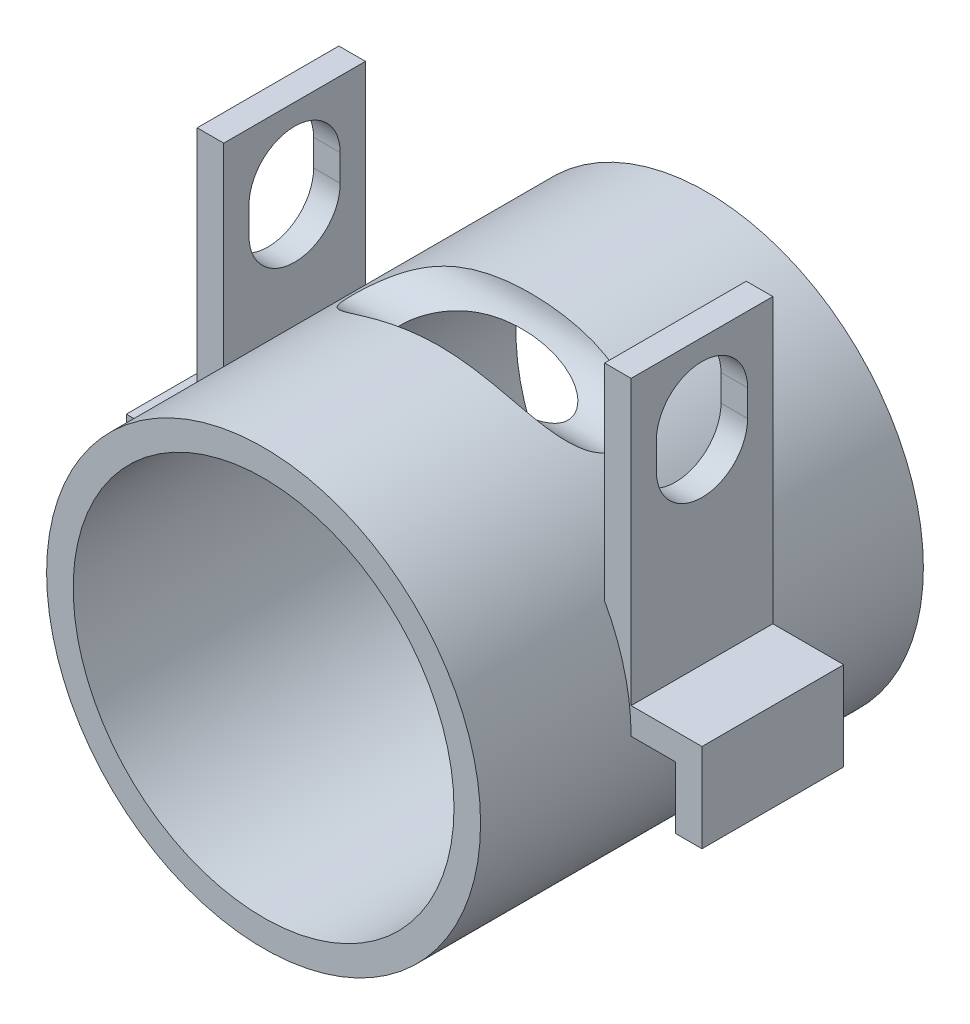
SolidWorks part; units mm, degrees
ref_plane "Front Plane" through (0, 0, 0) normal (0, 0, 1) x (1, 0, 0)
ref_plane "Top Plane" through (0, 0, 0) normal (0, 1, 0) x (1, 0, 0)
ref_plane "Right Plane" through (0, 0, 0) normal (1, 0, 0) x (0, 0, -1)
sketch "Sketch1" plane through (0, 0, 0) normal (0, 0, 1) x (1, 0, 0)
  circle A0 centre (0, 0) radius 21.5
  circle A1 centre (0, 0) radius 24.5
  dimension "D1" = 43
  dimension "D2" = 3
extrude "Boss-Extrude1" add sketch "Sketch1" along normal blind 50
ref_plane "Plane1" through (0, 0, 25) normal (0, 0, 1) x (1, 0, 0)
sketch "Sketch3" plane through (0, 0, 0) normal (1, 0, 0) x (0, 0, -1)
  line L0 (0, 24.5) -> (-50, 24.5) construction
  circle A0 centre (-25, 24.5) radius 5.15
  dimension "D1" = 10.3
extrude "Cut-Extrude1" cut sketch "Sketch3" against normal mid plane 50
sketch "Sketch4" plane through (0, 0, 25) normal (0, 0, 1) x (1, 0, 0)
  line L3 (0, 0) -> (50000, 0) construction
  line L4 (-19.776, 24.5) -> (49980.224, 24.5) construction
  line L5 (-21.5, 11.7473) -> (-21.5, 35)
  line L6 (-24.5, 0) -> (-24.5, 35)
  line L7 (-24.5, 35) -> (-21.5, 35)
  line L8 (0, 0) -> (0, 11.0861) construction
  circle A3 centre (0, 0) radius 24.5 construction
  arc A4 (-21.5, 11.7473) -> (-24.5, 0) centre (0, 0) ccw
  dimension "D1" = 3
  dimension "D2" = 35
extrude "Boss-Extrude2" add sketch "Sketch4" along normal mid plane 16
sketch "Sketch6" plane through (0, 0, 25) normal (0, 0, 1) x (1, 0, 0)
  line L0 (-24.5, 35) -> (-24.5, 0) construction
  line L1 (-24.5, 0) -> (-32.5, 0)
  line L2 (-24.5, 0) -> (-24.5, 3)
  line L3 (-24.5, 3) -> (-32.5, 3)
  line L4 (-32.5, 0) -> (-32.5, 3)
  line L5 (-24.5, 0) -> (-32.5, 3) construction
  line L6 (-24.5, 3) -> (-32.5, 0) construction
  line L7 (-32.5, 0) -> (-29.5, 0)
  line L8 (-32.5, 0) -> (-32.5, -7)
  line L9 (-32.5, -7) -> (-29.5, -7)
  line L10 (-29.5, 0) -> (-29.5, -7)
  line L11 (-32.5, 0) -> (-29.5, -7) construction
  line L12 (-32.5, -7) -> (-29.5, 0) construction
  circle A0 centre (0, 0) radius 24.5 construction
  arc A1 (-21.5, 11.7473) -> (-24.5, 0) centre (0, 0) ccw construction
  point P4 (-28.5, 1.5)
  point P13 (-31, -3.5)
  point P14 (-28.8209, -1.2714)
  point P15 (0, 0)
  dimension "D1" = 8
  dimension "D2" = 3
  dimension "D3" = 7
  dimension "D4" = 3
extrude "Boss-Extrude3" add sketch "Sketch6" along normal mid plane 16 contours L4 L1 L2 L3 | L10 L1 L8 L9 region at (-28.5, 1.5, 25) region at (-31, -3.5, 25)
mirror "Mirror1" about plane through (0, 0, 0) normal (1, 0, 0) of "Boss-Extrude3", "Boss-Extrude2"
sketch "Sketch5" plane through (-24.5, 0, 0) normal (-1, 0, 0) x (0, 0, 1)
  line L0 (25, -26.95) -> (25, 26.95) construction
  line L1 (25, 24.5) -> (25, 27.5) construction
  line L6 (19.85, 24.5) -> (19.85, 27.5)
  line L7 (30.15, 24.5) -> (30.15, 27.5)
  circle A0 centre (25, 24.5) radius 5.15 construction
  arc A1 (30.15, 24.5) -> (19.85, 24.5) centre (25, 24.5) ccw construction
  arc A2 (19.85, 24.5) -> (30.15, 24.5) centre (25, 24.5) ccw
  arc A3 (30.15, 27.5) -> (19.85, 27.5) centre (25, 27.5) ccw
  point P7 (25, 26)
  dimension "D1" = 3
extrude "Cut-Extrude3" cut sketch "Sketch5" against normal through all
